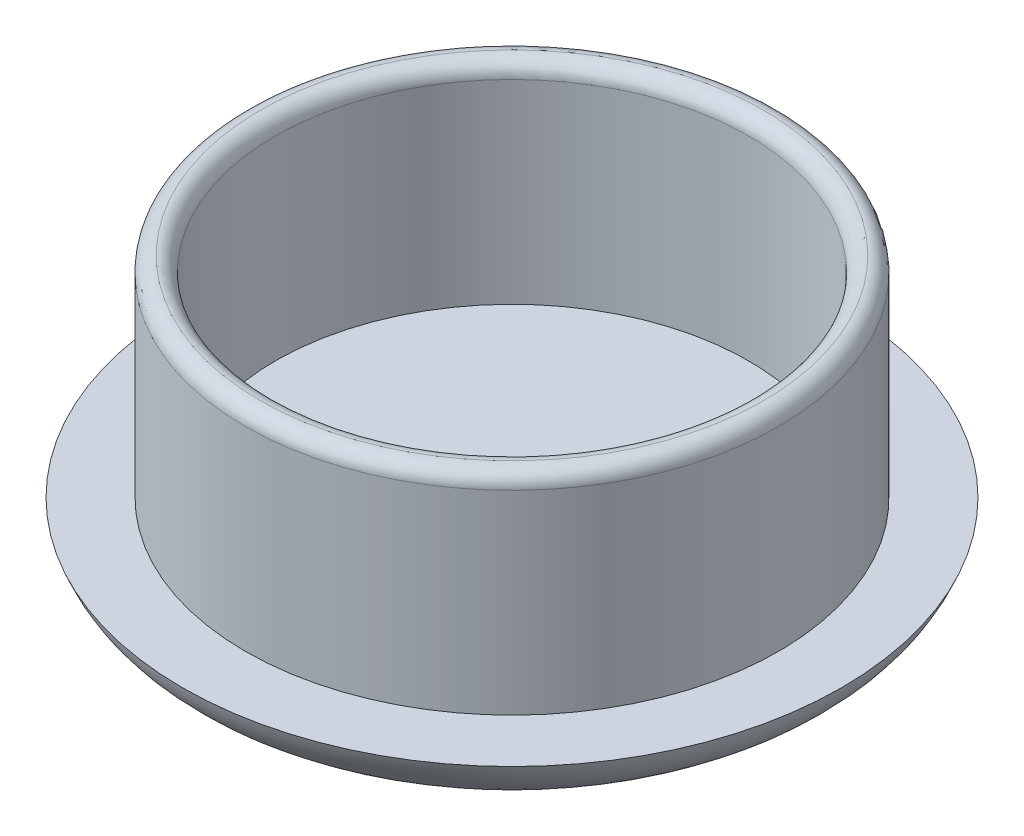
SolidWorks part; units mm, degrees
ref_plane "Front Plane" through (0, 0, 0) normal (0, 0, 1) x (1, 0, 0)
ref_plane "Top Plane" through (0, 0, 0) normal (0, 1, 0) x (1, 0, 0)
ref_plane "Right Plane" through (0, 0, 0) normal (1, 0, 0) x (0, 0, -1)
sketch "Sketch1" plane through (0, 0, 0) normal (0, 1, 0) x (1, 0, 0)
  circle A0 centre (0, 0) radius 11
  dimension "D1" = 22
extrude "Boss-Extrude1" add sketch "Sketch1" along normal blind 2
sketch "Sketch2" plane through (0, 2, 0) normal (0, 1, 0) x (1, 0, 0)
  circle A0 centre (0, 0) radius 8.9
  circle A1 centre (0, 0) radius 7.9
  dimension "D1" = 17.8
  dimension "D2" = 15.8
extrude "Boss-Extrude2" add sketch "Sketch2" along normal blind 7
sketch "Sketch3" plane through (0, 2, 0) normal (0, 1, 0) x (1, 0, 0)
  circle A0 centre (0, 0) radius 1.65
  dimension "D1" = 3.3
extrude "Cut-Extrude1" cut sketch "Sketch3" against normal through all
fillet "Fillet1" radius 3 1 edges at (0, 0, 11)
fillet "Fillet2" radius 0.5 2 edges at (0, 9, 7.9) (0, 9, 8.9)
